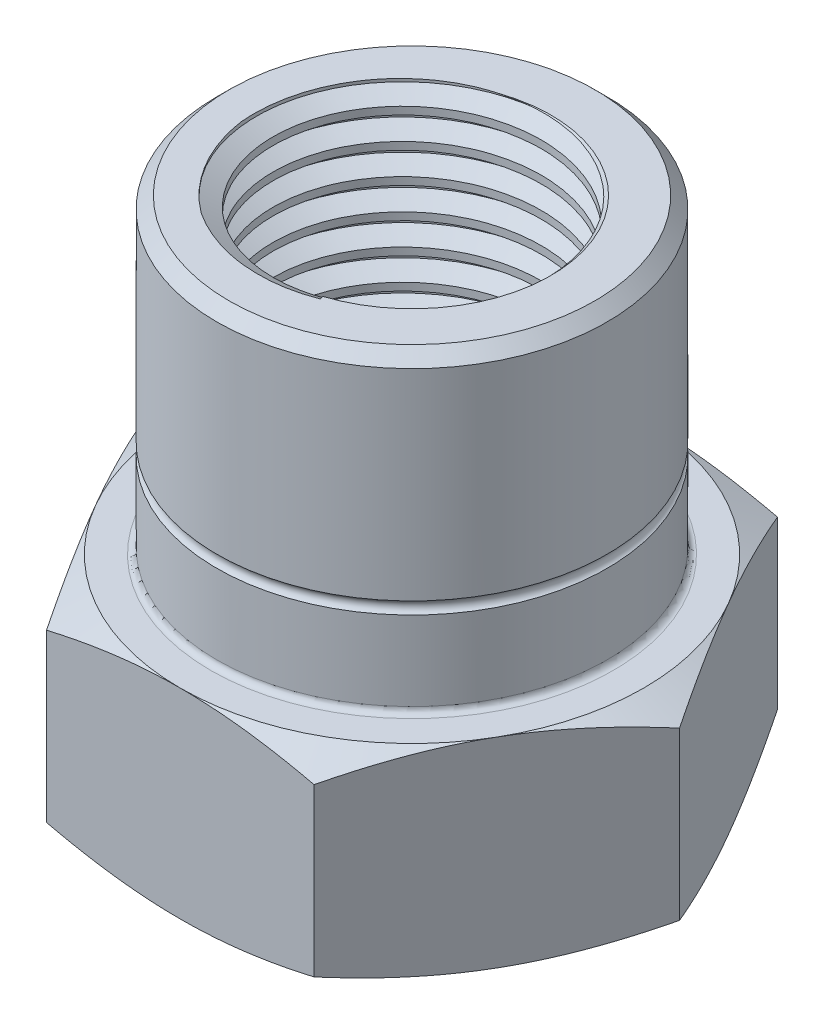
SolidWorks part; units mm, degrees
material "6061-T6 (SS)"
ref_plane "Front Plane" through (0, 0, 0) normal (0, 0, 1) x (1, 0, 0)
ref_plane "Top Plane" through (0, 0, 0) normal (0, 1, 0) x (1, 0, 0)
ref_plane "Right Plane" through (0, 0, 0) normal (1, 0, 0) x (0, 0, -1)
sketch "Sketch1" plane through (0, 0, 0) normal (0, 1, 0) x (1, 0, 0)
  line L1 (10.9697, 0) -> (5.4848, 9.5)
  line L2 (5.4848, 9.5) -> (-5.4848, 9.5)
  line L3 (-5.4848, 9.5) -> (-10.9697, 0)
  line L4 (-10.9697, 0) -> (-5.4848, -9.5)
  line L5 (-5.4848, -9.5) -> (5.4848, -9.5)
  line L6 (5.4848, -9.5) -> (10.9697, 0)
  circle A0 centre (0, 0) radius 9.5 construction
  dimension "D1" = 19
extrude "Boss-Extrude1" add sketch "Sketch1" along normal blind 8.2
sketch "Sketch2" plane through (0, 0, 0) normal (0, -1, 0) x (1, 0, 0)
  circle A0 centre (0, 0) radius 9.5
extrude "Cut-Extrude1" cut sketch "Sketch2" against normal blind 1 draft 65 flip side to cut
sketch "Sketch3" plane through (0, 8.2, 0) normal (0, 1, 0) x (1, 0, 0)
  circle A1 centre (0, 0) radius 9.5
  circle A2 centre (0, 0) radius 9.5
  dimension "D1" = 0
extrude "Cut-Extrude2" cut sketch "Sketch3" against normal blind 1 draft 65 flip side to cut
sketch "Sketch4" plane through (0, 8.2, 0) normal (0, 1, 0) x (1, 0, 0)
  circle A0 centre (0, 0) radius 8
  dimension "D1" = 16
extrude "Boss-Extrude2" add sketch "Sketch4" along normal blind 12.75
chamfer "Chamfer1" distance 0.5 angle 45 1 edges at (0, 20.95, 8)
fillet "Fillet1" radius 0.25 1 edges at (0, 8.2, 8)
sketch "Sketch7" plane through (0, 0, 0) normal (0, -1, 0) x (-1, 0, 0)
  point P0 (0, 0)
hole_wizard "M10 Clearance Hole1" positions "Sketch7" profile "Sketch6" hole size "M10" standard "ANSI Metric" end condition through all
sketch "Sketch6" plane through (0, 0, 0) normal (1, 0, 0) x (0, 0, -1)
  line L0 (0, 0) -> (0, 20.95)
  line L1 (0, 20.95) -> (5.5, 20.95)
  line L2 (5.5, 20.95) -> (5.5, 0)
  line L5 (5.5, 0) -> (0, 0)
  line L11 (0, -6.35) -> (0, 107.95) construction
  dimension "Thru Hole Dia." = 11
  dimension "Thru Hole Depth" = 20.95
chamfer "Chamfer2" distance 1 angle 45 1 edges at (0, 0, -5.5)
chamfer "Chamfer3" distance 0.2 angle 45 1 edges at (0, 20.95, -5.5)
thread "Thread1" pitch 1.25 method cut profile "Thread Profile1" start angle 0, offset 0, length 0, pitch 1.25, diameter 11
ref_plane "Plane1" through (5.5, 1, 0) normal (0, 0, 1) x (1, 0, 0)
sketch "Thread Profile1" plane through (5.5, 1, 0) normal (0, 0, 1) x (1, 0, 0)
  line L0 (0, 0) -> (0, 1.25) construction
  line L1 (0, 0) -> (0.6766, 0.3906)
  line L2 (0.6766, 0.3906) -> (0.6766, 0.5469)
  line L3 (0.6766, 0.5469) -> (0, 0.9375)
  line L4 (0.6766, 0.4687) -> (0, 0.4687) construction
  line L11 (0, 0) -> (0, 0.9375)
  point P2 (0, 0)
  dimension "Pitch" = 1.25
  dimension "Profile_Angle" = 60
  dimension "Profile_Land" = 0.1562
  dimension "Profile_Height" = 0.6766
sketch "Sketch11" plane through (0, 0, 0) normal (0, 0, 1) x (1, 0, 0)
  line L0 (0, 0) -> (0, -50000) construction
  line L1 (-8, 12.2) -> (-8, 11.7)
  line L2 (-8, 20.45) -> (-8, 8.45) construction
  line L4 (-8.2272, 8.2) -> (-9.5, 8.2) construction
  arc A0 (-8, 12.2) -> (-8, 11.7) centre (-8.1333, 11.95) cw
  point P10 (-7.85, 11.95)
  dimension "D1" = 3.5
  dimension "D2" = 0.15
  dimension "D3" = 0.5
revolve "Cut-Revolve1" cut sketch "Sketch11" angle 360 about L0
